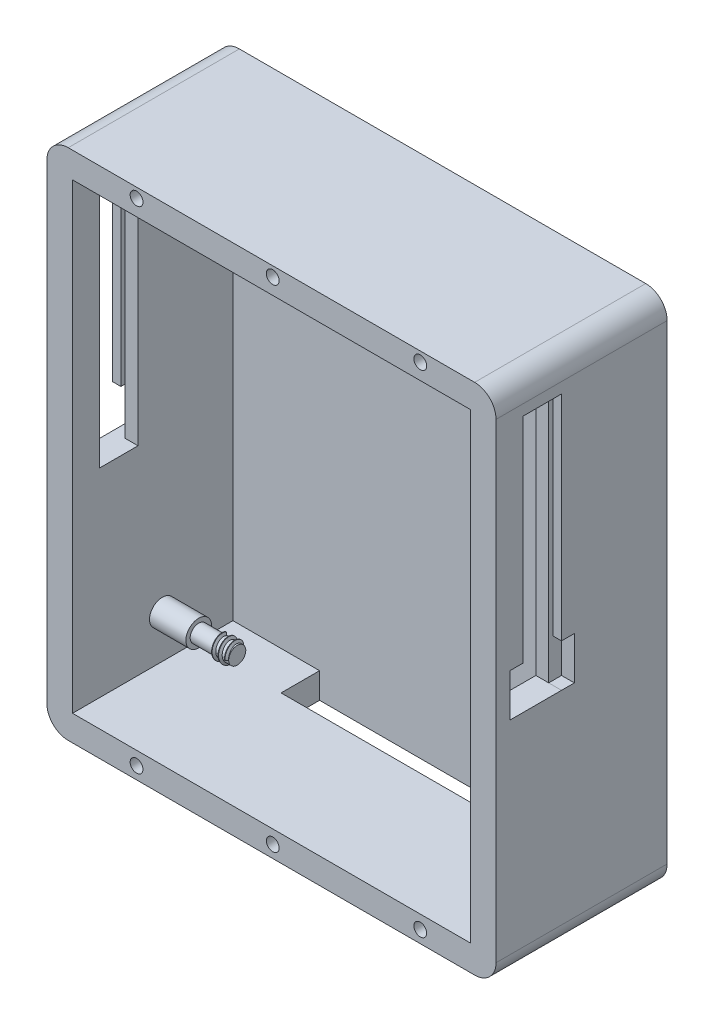
SolidWorks part; units mm, degrees
ref_plane "Ön Düzlem" through (0, 0, 0) normal (0, 0, 1) x (1, 0, 0)
ref_plane "Üst Düzlem" through (0, 0, 0) normal (0, 1, 0) x (1, 0, 0)
ref_plane "Sağ Düzlem" through (0, 0, 0) normal (1, 0, 0) x (0, 0, -1)
sketch "Çizim1" plane through (0, 0, 0) normal (0, 0, 1) x (1, 0, 0)
  line L0 (-157.0242, 36) -> (-157.0242, 0)
  line L1 (-157.0242, 0) -> (52.9758, 0)
  line L2 (-157.0242, 36) -> (-145.0242, 36)
  line L3 (-145.0242, 36) -> (-145.0242, 12)
  line L4 (-145.0242, 12) -> (40.9758, 12)
  line L5 (52.9758, 0) -> (52.9758, 36)
  line L6 (52.9758, 36) -> (40.9758, 36)
  line L7 (40.9758, 36) -> (40.9758, 12)
  dimension "D1" = 36
  dimension "D2" = 210
  dimension "D3" = 12
  dimension "D4" = 24
  dimension "D5" = 186
extrude "Yükseklik-Ekstrüzyon1" add sketch "Çizim1" along normal blind 75
sketch "Çizim2" plane through (-145.0242, 0, 0) normal (1, 0, 0) x (0, 0, -1)
  line L0 (-75, 12) -> (0, 12) construction
  line L1 (-75, 12) -> (-75, 36) construction
  circle A0 centre (-33, 32) radius 6
  dimension "D1" = 12
  dimension "D2" = 12
  dimension "D3" = 20
  dimension "D4" = 42
extrude "Yükseklik-Ekstrüzyon2" add sketch "Çizim2" along normal blind 17
sketch "Çizim3" plane through (-128.0242, 0, 0) normal (1, 0, 0) x (0, 0, -1)
  circle A0 centre (-33, 32) radius 4
  circle A1 centre (-33, 32) radius 6 construction
  point P2 (-32.492, 32.006)
  point P5 (0, 0)
  dimension "D1" = 8
  dimension "D2" = 0
extrude "Yükseklik-Ekstrüzyon3" add sketch "Çizim3" along normal blind 18
sketch "Çizim4" plane through (40.9758, 0, 0) normal (-1, 0, 0) x (0, 0, 1)
  line L0 (75, 12) -> (0, 12) construction
  line L3 (75, 36) -> (75, 12) construction
  circle A0 centre (33, 32) radius 6
  dimension "D1" = 20
  dimension "D2" = 42
extrude "Yükseklik-Ekstrüzyon4" add sketch "Çizim4" along normal blind 17
sketch "Çizim5" plane through (23.9758, 0, 0) normal (-1, 0, 0) x (0, 0, 1)
  circle A0 centre (33, 32) radius 4
  circle A1 centre (33, 32) radius 6 construction
extrude "Yükseklik-Ekstrüzyon5" add sketch "Çizim5" along normal blind 18
thread "Diş1" pitch 2 method extrude profile "Diş Profili1" start angle 0, offset 0, length 7, pitch 3, diameter 8
ref_plane "Düzlem1" through (-110.0242, 32, 37) normal (0, -1, 0) x (0, 0, 1)
sketch "Diş Profili1" plane through (-110.0242, 32, 37) normal (0, -1, 0) x (0, 0, 1)
  line L0 (0, 0) -> (0, 2) construction
  line L1 (0, 0) -> (1.0825, 0.625)
  line L2 (1.0825, 0.625) -> (1.0825, 0.875)
  line L3 (1.0825, 0.875) -> (0, 1.5)
  line L4 (1.0825, 0.75) -> (0, 0.75) construction
  line L11 (0, 0) -> (0, 1.5)
  point P2 (0, 0)
  dimension "Pitch" = 2
  dimension "Profile_Angle" = 60
  dimension "Profile_Land" = 0.25
  dimension "Profile_Height" = 1.0825
thread "Diş2" pitch 2 method extrude profile "Diş Profili2" start angle 0, offset 0, length 7, pitch 3, diameter 8
ref_plane "Düzlem2" through (5.9758, 32, 29) normal (0, -1, 0) x (0, 0, -1)
sketch "Diş Profili2" plane through (5.9758, 32, 29) normal (0, -1, 0) x (0, 0, -1)
  line L0 (0, 0) -> (0, 2) construction
  line L1 (0, 0) -> (1.0825, 0.625)
  line L2 (1.0825, 0.625) -> (1.0825, 0.875)
  line L3 (1.0825, 0.875) -> (0, 1.5)
  line L4 (1.0825, 0.75) -> (0, 0.75) construction
  line L11 (0, 0) -> (0, 1.5)
  point P2 (0, 0)
  dimension "Pitch" = 2
  dimension "Profile_Angle" = 60
  dimension "Profile_Land" = 0.25
  dimension "Profile_Height" = 1.0825
sketch "Çizim10" plane through (0, 36, 0) normal (0, 1, 0) x (1, 0, 0)
  line L0 (-157.0242, 0) -> (-145.0242, 0)
  line L1 (-145.0242, 0) -> (-145.0242, -75)
  line L2 (-145.0242, -75) -> (-157.0242, -75)
  line L3 (-157.0242, -75) -> (-157.0242, 0)
extrude "Yükseklik-Ekstrüzyon6" add sketch "Çizim10" along normal blind 204
sketch "Çizim11" plane through (0, 36, 0) normal (0, 1, 0) x (1, 0, 0)
  line L0 (40.9758, 0) -> (52.9758, 0)
  line L1 (52.9758, 0) -> (52.9758, -75)
  line L2 (52.9758, -75) -> (40.9758, -75)
  line L3 (40.9758, -75) -> (40.9758, 0)
extrude "Yükseklik-Ekstrüzyon7" add sketch "Çizim11" along normal blind 204
sketch "Çizim12" plane through (0, 240, 0) normal (0, 1, 0) x (1, 0, 0)
  line L0 (-157.0242, 0) -> (52.9758, 0)
  line L1 (52.9758, 0) -> (52.9758, -75)
  line L2 (52.9758, -75) -> (-157.0242, -75)
  line L3 (-157.0242, -75) -> (-157.0242, 0)
extrude "Yükseklik-Ekstrüzyon8" add sketch "Çizim12" against normal blind 12
ref_plane "Düzlem5" through (0.4758, 0, 0) normal (1, 0, 0) x (0, 0, -1)
sketch "Çizim14" plane through (0.4758, 0, 0) normal (1, 0, 0) x (0, 0, -1)
  line L0 (0, 0) -> (0, 12)
  line L1 (0, 12) -> (-18, 12)
  line L2 (-18, 12) -> (-18, 0)
  line L3 (-18, 0) -> (0, 0)
  dimension "D1" = 12
  dimension "D2" = 18
extrude "Kes-Ekstrüzyon1" cut sketch "Çizim14" against normal blind 105
sketch "Çizim15" plane through (0, 0, 0) normal (0, 0, -1) x (-1, 0, 0)
  line L0 (-52.9758, 0) -> (157.0242, 0)
  line L1 (157.0242, 0) -> (157.0242, 240)
  line L2 (157.0242, 240) -> (-52.9758, 240)
  line L3 (-52.9758, 240) -> (-52.9758, 0)
extrude "Yükseklik-Ekstrüzyon9" add sketch "Çizim15" along normal blind 5
sketch "Çizim16" plane through (52.9758, 0, 0) normal (1, 0, 0) x (0, 0, -1)
  line L0 (-44.38, 225) -> (-62.38, 225)
  line L1 (-62.38, 225) -> (-62.38, 105)
  line L2 (-75, 0) -> (-75, 240) construction
  line L3 (-75, 240) -> (5, 240) construction
  line L4 (-44.38, 225) -> (-44.38, 105)
  line L5 (-44.38, 105) -> (-62.38, 105)
  dimension "D1" = 12.62
  dimension "D2" = 18
  dimension "D3" = 120
  dimension "D4" = 15
extrude "Kes-Ekstrüzyon2" cut sketch "Çizim16" against normal blind 12
sketch "Çizim17" plane through (-157.0242, 0, 0) normal (-1, 0, 0) x (0, 0, 1)
  line L0 (44.38, 105) -> (44.38, 225)
  line L1 (44.38, 225) -> (62.38, 225)
  line L2 (-5, 240) -> (75, 240) construction
  line L3 (44.38, 105) -> (62.38, 105)
  line L4 (62.38, 105) -> (62.38, 225)
  line L5 (75, 240) -> (75, 0) construction
  dimension "D1" = 120
  dimension "D2" = 18
  dimension "D3" = 15
  dimension "D4" = 12.62
extrude "Kes-Ekstrüzyon3" cut sketch "Çizim17" against normal blind 12
sketch "Çizim18" plane through (-157.0242, 0, 0) normal (-1, 0, 0) x (0, 0, 1)
  line L0 (62.38, 105) -> (68.38, 105)
  line L1 (68.38, 105) -> (68.38, 225)
  line L2 (68.38, 225) -> (62.38, 225)
  line L3 (62.38, 105) -> (62.38, 225)
  dimension "D1" = 6
extrude "Kes-Ekstrüzyon6" cut sketch "Çizim18" against normal blind 6
sketch "Çizim19" plane through (-157.0242, 0, 0) normal (-1, 0, 0) x (0, 0, 1)
  line L0 (44.38, 105) -> (38.38, 105)
  line L1 (38.38, 105) -> (38.38, 225)
  line L2 (38.38, 225) -> (44.38, 225)
  line L3 (44.38, 225) -> (44.38, 105)
  dimension "D1" = 6
extrude "Kes-Ekstrüzyon7" cut sketch "Çizim19" against normal blind 6
sketch "Çizim20" plane through (52.9758, 0, 0) normal (1, 0, 0) x (0, 0, -1)
  line L0 (-62.38, 225) -> (-68.38, 225)
  line L1 (-68.38, 225) -> (-68.38, 105)
  line L2 (-68.38, 105) -> (-62.38, 105)
  line L3 (-62.38, 105) -> (-62.38, 225)
  dimension "D1" = 6
extrude "Kes-Ekstrüzyon8" cut sketch "Çizim20" against normal blind 6
sketch "Çizim21" plane through (52.9758, 0, 0) normal (1, 0, 0) x (0, 0, -1)
  line L0 (-44.38, 225) -> (-38.38, 225)
  line L1 (-38.38, 225) -> (-38.38, 105.0034)
  line L2 (-38.38, 105.0034) -> (-44.38, 105)
  line L3 (-44.38, 105) -> (-44.38, 225)
  dimension "D1" = 6
extrude "Kes-Ekstrüzyon9" cut sketch "Çizim21" against normal blind 6
sketch "Çizim22" plane through (0, 0, 38.38) normal (0, 0, 1) x (1, 0, 0)
  line L6 (52.9758, 225) -> (48.9758, 225)
  line L7 (46.9758, 225) -> (52.9758, 225) construction
  line L8 (52.9758, 225) -> (52.9758, 125)
  line L9 (52.9758, 105.0034) -> (52.9758, 225) construction
  line L10 (52.9758, 125) -> (48.9758, 125)
  line L11 (48.9758, 125) -> (48.9758, 225)
  dimension "D1" = 4
  dimension "D2" = 100
extrude "Yükseklik-Ekstrüzyon10" add sketch "Çizim22" along normal blind 6
sketch "Çizim23" plane through (0, 0, 68.38) normal (0, 0, -1) x (-1, 0, 0)
  line L1 (-52.9758, 225) -> (-52.9758, 105) construction
  line L4 (-52.9758, 125) -> (-48.9758, 125)
  line L6 (-52.9758, 225) -> (-48.9758, 225)
  line L7 (-46.9758, 225) -> (-52.9758, 225) construction
  line L8 (-52.9758, 225) -> (-52.9758, 125)
  line L9 (-48.9758, 125) -> (-48.9758, 225)
  dimension "D1" = 4
  dimension "D2" = 100
extrude "Yükseklik-Ekstrüzyon11" add sketch "Çizim23" along normal blind 6
sketch "Çizim24" plane through (0, 0, 68.38) normal (0, 0, -1) x (-1, 0, 0)
  line L1 (157.0242, 125) -> (157.0242, 225)
  line L6 (157.0242, 225) -> (153.0242, 225)
  line L7 (151.0242, 225) -> (157.0242, 225) construction
  line L8 (153.0242, 225) -> (153.0242, 125)
  line L9 (153.0242, 125) -> (157.0242, 125)
  line L10 (157.0242, 105) -> (157.0242, 225) construction
extrude "Yükseklik-Ekstrüzyon12" add sketch "Çizim24" along normal blind 6
sketch "Çizim25" plane through (0, 0, 38.38) normal (0, 0, 1) x (1, 0, 0)
  line L1 (-157.0242, 125) -> (-157.0242, 225)
  line L6 (-157.0242, 225) -> (-153.0242, 225)
  line L7 (-151.0242, 225) -> (-157.0242, 225) construction
  line L8 (-153.0242, 225) -> (-153.0242, 125)
  line L9 (-153.0242, 125) -> (-157.0242, 125)
  line L10 (-157.0242, 225) -> (-157.0242, 105) construction
  dimension "D1" = 4
extrude "Yükseklik-Ekstrüzyon13" add sketch "Çizim25" along normal blind 6
sketch "Çizim35" plane through (0, 0, 75) normal (0, 0, 1) x (1, 0, 0)
  point P0 (-115.0832, 5.7364)
  point P1 (-51.4189, 5.7364)
  point P2 (17.5557, 5.7364)
  point P3 (17.5557, 235.4063)
  point P4 (-51.4189, 235.4063)
  point P5 (-115.0832, 235.4063)
hole_wizard "M16 Helisarmal için Zıvana matkabı2" positions "3B Çizim5" profile "Çizim37" hole size "M16x1.5" standard "ANSI Metrik"
sketch3d "3B Çizim5"
  point P0 (-115.0832, 5.7364, 75)
  point P3 (-51.4189, 5.7364, 75)
  point P6 (17.5557, 5.7364, 75)
  point P9 (-115.0832, 235.4063, 75)
  point P12 (-51.4189, 235.4063, 75)
  point P15 (17.5557, 235.4063, 75)
sketch "Çizim37" plane through (-115.0832, 5.7364, 75) normal (1, 0, 0) x (0, -1, 0)
  line L0 (0, 0) -> (0, 13.8026)
  line L1 (0, 13.8026) -> (3, 12)
  line L2 (3, 12) -> (3, 0)
  line L5 (3, 0) -> (0, 0)
  line L10 (0, 13.8026) -> (-3, 12) construction
  line L11 (0, -6.35) -> (0, 107.95) construction
  dimension "Hole Dia." = 6
  dimension "Hole Depth" = 12
  dimension "Drill Angle" = 118
fillet "Radyus1" radius 10 4 edges at (52.9758, 240, 35) (52.9758, 0, 35) (-157.0242, 0, 35) (-157.0242, 240, 35)
